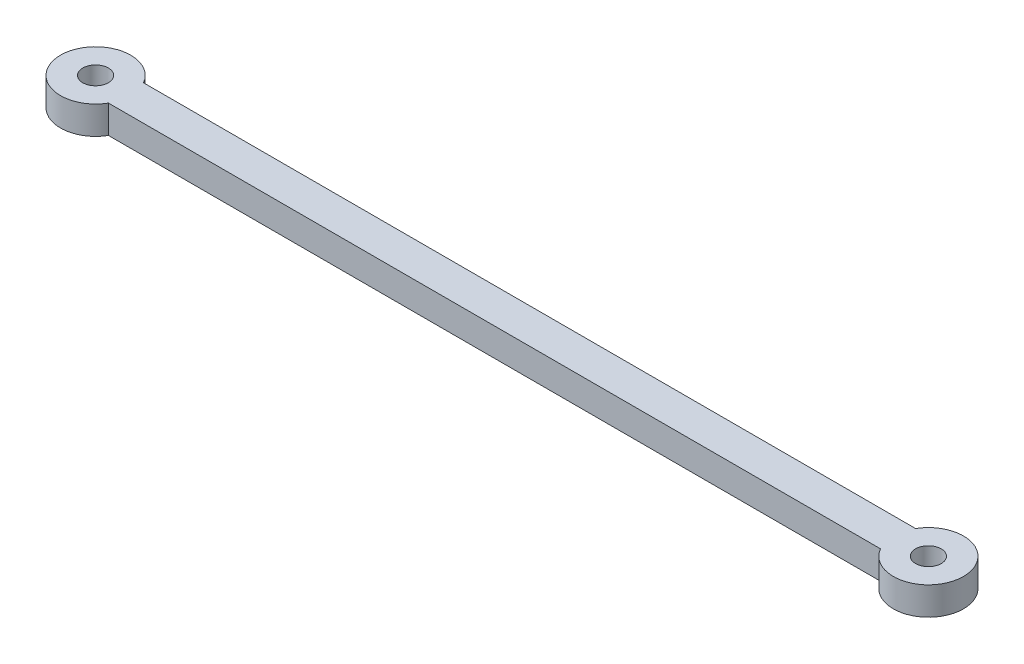
SolidWorks part; units mm, degrees
ref_plane "Front Plane" through (0, 0, 0) normal (0, 0, 1) x (1, 0, 0)
ref_plane "Top Plane" through (0, 0, 0) normal (0, 1, 0) x (1, 0, 0)
ref_plane "Right Plane" through (0, 0, 0) normal (1, 0, 0) x (0, 0, -1)
sketch "Sketch1" plane through (0, 0, 0) normal (0, 1, 0) x (1, 0, 0)
  line L0 (-55, 2.5) -> (55, 2.5)
  line L1 (-55, -2.5) -> (55, -2.5)
  line L2 (-55, 0) -> (55, 0) construction
  arc A1 (-55, 2.5) -> (-55, -2.5) centre (-59.3301, 0) ccw
  arc A2 (55, 2.5) -> (55, -2.5) centre (59.3301, 0) cw
  dimension "D2" = 55
  dimension "D3" = 5
  dimension "D7" = 5
  dimension "D1" = 5
  dimension "D4" = 110
  dimension "D5" = 110
  dimension "D6" = 2.5
extrude "Boss-Extrude1" add sketch "Sketch1" along normal blind 4
sketch "Sketch2" plane through (0, 4, 0) normal (0, 1, 0) x (1, 0, 0)
  circle A0 centre (-59.3301, 0) radius 1.825
  circle A1 centre (59.3301, 0) radius 1.825
  dimension "D1" = 3.65
  dimension "D2" = 3.65
extrude "Cut-Extrude1" cut sketch "Sketch2" against normal through all
